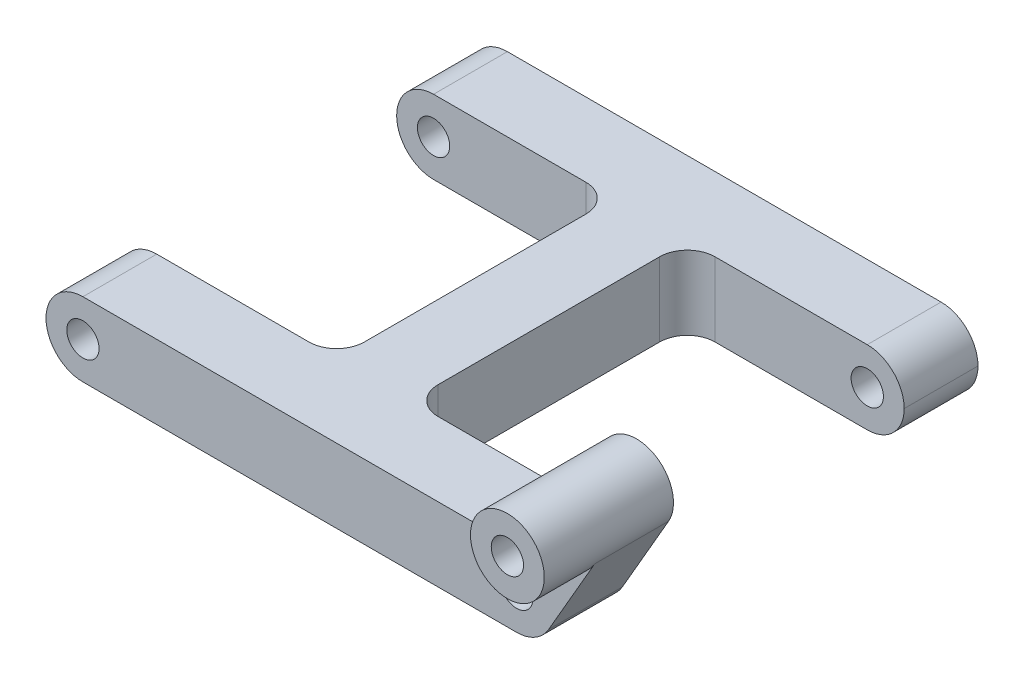
SolidWorks part; units mm, degrees
ref_plane "Alzado" through (0, 0, 0) normal (0, 0, 1) x (1, 0, 0)
ref_plane "Planta" through (0, 0, 0) normal (0, 1, 0) x (1, 0, 0)
ref_plane "Vista lateral" through (0, 0, 0) normal (1, 0, 0) x (0, 0, -1)
sketch "Croquis2" plane through (0, 0, 0) normal (0, 1, 0) x (1, 0, 0)
  line L5 (27.5, -23) -> (27.5, -15)
  line L6 (27.5, -15) -> (4, -15)
  line L7 (4, -15) -> (4, 15)
  line L8 (4, 15) -> (27.5, 15)
  line L9 (27.5, 15) -> (27.5, 23)
  line L24 (-35, 0) -> (35, 0) construction
  line L35 (27.5, 23) -> (-27.5, 23)
  line L36 (27.5, -23) -> (-27.5, -23)
  line L37 (-27.5, -23) -> (-27.5, -15)
  line L38 (-27.5, -15) -> (-4, -15)
  line L39 (-4, -15) -> (-4, 15)
  line L40 (-4, 15) -> (-27.5, 15)
  line L41 (-27.5, 15) -> (-27.5, 23)
  line L42 (0, 23) -> (0, -23) construction
  dimension "D1" = 55
  dimension "D2" = 55
  dimension "D3" = 4
  dimension "D4" = 4
  dimension "D5" = 8
  dimension "D6" = 8
  dimension "D7" = 23.5
  dimension "D8" = 30
  dimension "D9" = 30
extrude "Saliente-Extruir1" add sketch "Croquis2" along normal mid plane 8
sketch "Croquis3" plane through (0, 0, 23) normal (0, 0, 1) x (1, 0, 0)
  line L2 (-27.5, 4) -> (-27.5, -4) construction
  line L5 (27.5, 4) -> (27.5, -4) construction
  line L6 (-27.5, -4) -> (27.5, -4) construction
  circle A0 centre (23.5, 0) radius 1.75
  circle A1 centre (-23.5, 0) radius 1.75
  dimension "D1" = 3.5
  dimension "D2" = 3.5
  dimension "D3" = 4
  dimension "D6" = 4
  dimension "D4" = 4
  dimension "D5" = 4
extrude "Cortar-Extruir1" cut sketch "Croquis3" against normal through all
fillet "Redondeo8" radius 4 8 edges at (27.5, -4, -19) (27.5, 4, -19) (27.5, -4, 19) (27.5, 4, 19) (-27.5, -4, -19) (-27.5, 4, -19) (-27.5, -4, 19) (-27.5, 4, 19)
fillet "Redondeo9" radius 3 4 edges at (4, 0, 15) (4, 0, -15) (-4, 0, 15) (-4, 0, -15)
sketch "Croquis5" plane through (0, 0, -23) normal (0, 0, -1) x (-1, 0, 0)
  line L0 (-25.0359, 10.6603) -> (-20.0359, 2)
  line L1 (-31.9641, 6.6603) -> (-26.9641, -2)
  line L2 (-28.5, 8.6603) -> (-23.5, 0) construction
  circle A0 centre (-23.5, 0) radius 1.75
  circle A1 centre (-28.5, 8.6603) radius 1.75
  arc A2 (-25.0359, 10.6603) -> (-31.9641, 6.6603) centre (-28.5, 8.6603) ccw
  arc A3 (-26.9641, -2) -> (-20.0359, 2) centre (-23.5, 0) ccw
  dimension "D1" = 8
  dimension "D2" = 8
  dimension "D3" = 3.5
  dimension "D4" = 3.5
  dimension "D5" = 120
  dimension "D6" = 10
extrude "Saliente-Extruir3" add sketch "Croquis5" against normal blind 8 from surface starting at face at (25.25, 0, 15)
sketch "Croquis4" plane through (0, 0, -23) normal (0, 0, 1) x (1, 0, 0)
  circle A0 centre (28.5, 8.6603) radius 4
  circle A2 centre (28.5, 8.6603) radius 1.75
  dimension "D1" = 8
extrude "Saliente-Extruir2" add sketch "Croquis4" along normal blind 6 from surface starting at face at (6.8457, 2.2901, 23)
sketch "Croquis6" plane through (0, 0, -23) normal (0, 0, -1) x (-1, 0, 0)
  circle A0 centre (23.5, 0) radius 3.1
  dimension "D1" = 6.2
extrude "Cortar-Extruir2" cut sketch "Croquis6" against normal blind 3.2
